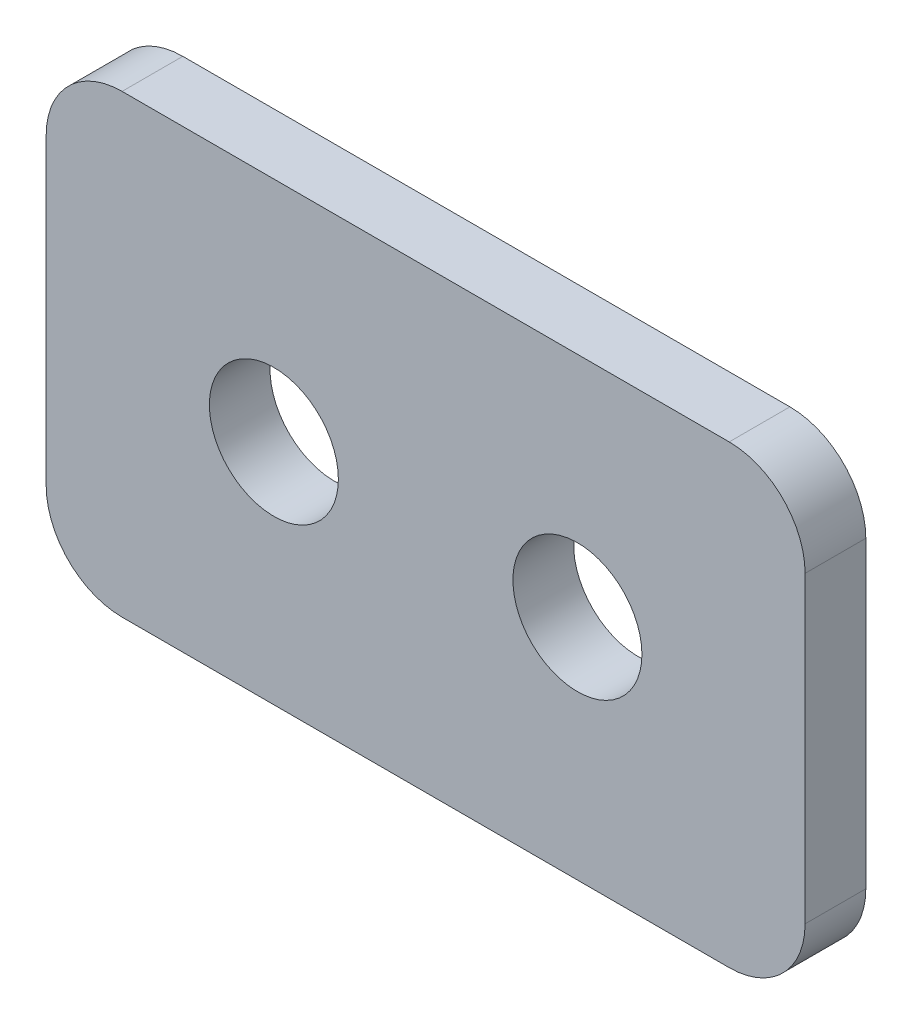
SolidWorks part; units mm, degrees
material "ASTM A36 Steel"
ref_plane "Front Plane" through (0, 0, 0) normal (0, 0, 1) x (1, 0, 0)
ref_plane "Top Plane" through (0, 0, 0) normal (0, 1, 0) x (1, 0, 0)
ref_plane "Right Plane" through (0, 0, 0) normal (1, 0, 0) x (0, 0, -1)
sketch "Sketch1" plane through (0, 0, 0) normal (0, 0, 1) x (1, 0, 0)
  line L1 (-20, -15) -> (20, -15)
  line L2 (-25, -10) -> (-25, 10)
  line L3 (-20, 15) -> (20, 15)
  line L4 (25, -10) -> (25, 10)
  line L5 (-25, -15) -> (25, 15) construction
  line L6 (-25, 15) -> (25, -15) construction
  arc A0 (-20, -15) -> (-25, -10) centre (-20, -10) cw
  arc A1 (20, -15) -> (25, -10) centre (20, -10) ccw
  arc A2 (20, 15) -> (25, 10) centre (20, 10) cw
  arc A3 (-25, 10) -> (-20, 15) centre (-20, 10) cw
  circle A4 centre (-10, 0) radius 4.25
  circle A5 centre (10, 0) radius 4.25
  point P0 (0, 0)
  dimension "D3" = 5
  dimension "D4" = 8.5
  dimension "D5" = 8.5
  dimension "D6" = 20
  dimension "D1" = 30
  dimension "D2" = 50
  dimension "D7" = 10
base flange "Base-Flange1" sketch "Sketch1" thickness 4 reverse thickness direction no parameters "D1"=0.7366
sketch "Bend-Lines1" [suppressed] plane through (0, 0, 0) normal (0, 1, 0) x (1, 0, 0)
sketch "Bounding-Box1" [suppressed] plane through (0, 0, 0) normal (0, 1, 0) x (1, 0, 0)
sheet metal parameters "Sheet-Metal1" thickness 4 parameters "D1"=0.7366
flat pattern "Flat-Pattern1" [suppressed]
sketch "Bend-Lines2" plane through (0, 0, 0) normal (0, 1, 0) x (1, 0, 0)
sketch3d "Bounding-Box2" [suppressed]
  line L0 (-5, 25, 0) -> (45, 25, 0) construction
  line L1 (-5, -5, 0) -> (45, -5, 0) construction
  line L2 (-5, 25, 0) -> (-5, -5, 0) construction
  line L3 (45, 25, 0) -> (45, -5, 0) construction
